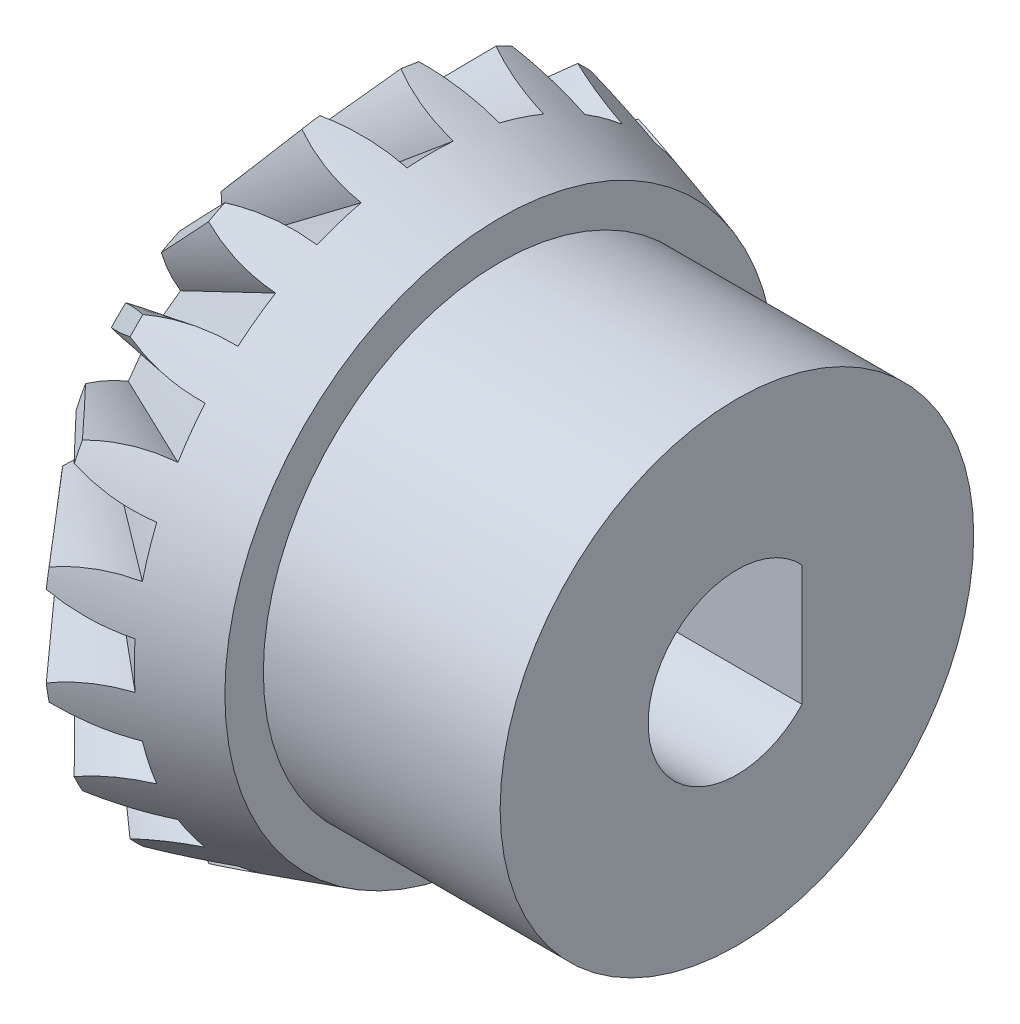
SolidWorks part; units mm, degrees
ref_plane "Front" through (0, 0, 0) normal (0, 0, 1) x (1, 0, 0)
ref_plane "Top" through (0, 0, 0) normal (0, 1, 0) x (1, 0, 0)
ref_plane "Right" through (0, 0, 0) normal (1, 0, 0) x (0, 0, -1)
sketch "Sketch1" plane through (0, 0, 0) normal (0, 0, 1) x (1, 0, 0)
  line L0 (0, 0) -> (8, 0) construction
  line L1 (0, 1.5) -> (8, 1.5)
  line L2 (8, 1.5) -> (8, 4)
  line L3 (8, 4) -> (4, 4)
  line L4 (4, 4) -> (4, 4.65)
  line L5 (4, 4.65) -> (1.6397, 5.35)
  line L6 (1.6397, 5.35) -> (0, 3.4628)
  line L7 (0, 3.4628) -> (0, 1.5)
  line L8 (2.8199, 5) -> (0, 1.7546) construction
  dimension "D1" = 49.013
  dimension "Overall Length" = 8
  dimension "OD" = 10.7
  dimension "For Shaft" = 3
  dimension "Face Width" = 2.5
  dimension "Hub Dia" = 8
  dimension "Hub Width" = 4
  dimension "PD" = 10
revolve "Revolve1" add sketch "Sketch1" angle 360 about L0
sketch "Sketch2" plane through (0, 0, 0) normal (-1, 0, 0) x (0, 0, 1)
  circle A0 centre (0, 0) radius 5
  dimension "Pitch Dia" = 10
sketch "Sketch3" plane through (0, 0, 0) normal (-1, 0, 0) x (0, 0, 1)
  line L0 (-10, 0) -> (10, 0) construction
  point P2 (0, 0)
  dimension "teeth" = 20
sketch "Sketch5" plane through (0, 0, 0) normal (-1, 0, 0) x (0, 0, 1)
  line L0 (0, 0) -> (0, 5.35) construction
  line L1 (0, 0) -> (0.4198, 5.3335) construction
  line L2 (0, 0) -> (-0.4198, 5.3335) construction
  line L4 (-10, 0) -> (10, 0) construction
  line L5 (-0.2099, 2.6668) -> (0.2099, 2.6668)
  line L6 (0, 0) -> (-1.6532, 5.0882) construction
  line L7 (0, 0) -> (1.6532, 5.0882) construction
  circle A0 centre (0, 0) radius 5.35 construction
  arc A1 (-0.2099, 2.6668) -> (-1.6532, 5.0882) centre (-3.3814, 2.4172) ccw
  arc A2 (0.2099, 2.6668) -> (1.6532, 5.0882) centre (3.3814, 2.4172) cw
  arc A3 (-1.6532, 5.0882) -> (1.6532, 5.0882) centre (0, 0) cw
  point P10 (0, 0)
  dimension "D1" = 9
  dimension "D2" = 36
ref_plane "Plane1" through (2.8199, 0, 0) normal (1, 0, 0) x (0, 0, -1)
sketch "Sketch6" plane through (2.8199, 0, 0) normal (1, 0, 0) x (0, 0, -1)
  line L0 (0, 0) -> (0, 8.025) construction
  line L1 (0, 0) -> (0.4198, 5.3335) construction
  line L2 (0, 0) -> (-0.4198, 5.3335) construction
  line L3 (0, 0) -> (2.6075, 8.025) construction
  line L4 (0, 0) -> (-2.6075, 8.025) construction
  line L5 (2.6075, 8.025) -> (-2.6075, 8.025) construction
  line L6 (0, 5.35) -> (0, 0) construction
  line L7 (-2.6075, 8.025) -> (2.6075, 8.025)
  circle A0 centre (0, 0) radius 5.35 construction
  arc A1 (-0.3923, 4.9846) -> (-2.6075, 8.025) centre (-3.9732, 4.7028) ccw
  arc A2 (0.3923, 4.9846) -> (2.6075, 8.025) centre (3.9732, 4.7028) cw
  circle A3 centre (0, 0) radius 5 construction
  arc A4 (0.3923, 4.9846) -> (-0.3923, 4.9846) centre (0, 0) ccw
  dimension "D1" = 9
  dimension "D2" = 36
  dimension "D3" = 8.025
  dimension "D4" = 5.35
loft "Cut-Loft1" cut profiles "Sketch6", "Sketch5" connector at (2.8199, 8.025, -2.6075) connector at (0, 5.0882, -1.6532)
pattern_circular "CirPattern1" count 20 over 360 about axis through (0, 0, 0) along (-1, 0, 0) of "Cut-Loft1"
sketch "Sketch7" plane through (0, 0, 0) normal (-1, 0, 0) x (0, 0, 1)
  circle A0 centre (0, 0) radius 5
sketch "Sketch8"
  dimension "D1" = 11
sketch_block_instance "Block1-1"
sketch_block "Block1"
sketch "Sketch10" plane through (8, 0, 0) normal (1, 0, 0) x (0, 0, -1)
  line L0 (-1.5, 0) -> (1.5, 0) construction
  line L1 (1.1, 1.0198) -> (1.1, -1.0198)
  circle A0 centre (0, 0) radius 1.5 construction
  arc A1 (1.1, -1.0198) -> (1.1, 1.0198) centre (0, 0) ccw
  dimension "D1" = 0.4
extrude "Boss-Extrude1" add sketch "Sketch10" against normal up to surface (8 mm away) up to face at (0, 0, 1.5)
equation "\"D1@Sketch5\"=(360deg/20)/2"
equation "\"D2@Sketch5\"=(360deg/20)/.5"
equation "\"D1@Sketch6\"=(360deg/\"teeth@Sketch5\")/2"
equation "\"D2@Sketch6\"=(360deg/\"teeth@Sketch5\")/.5"
equation "\"D3@Sketch6\"=\"D4@Sketch6\"*1.5"
equation "\"D1@Sketch8\"=\"Mounting Distance@Sketch8\""
